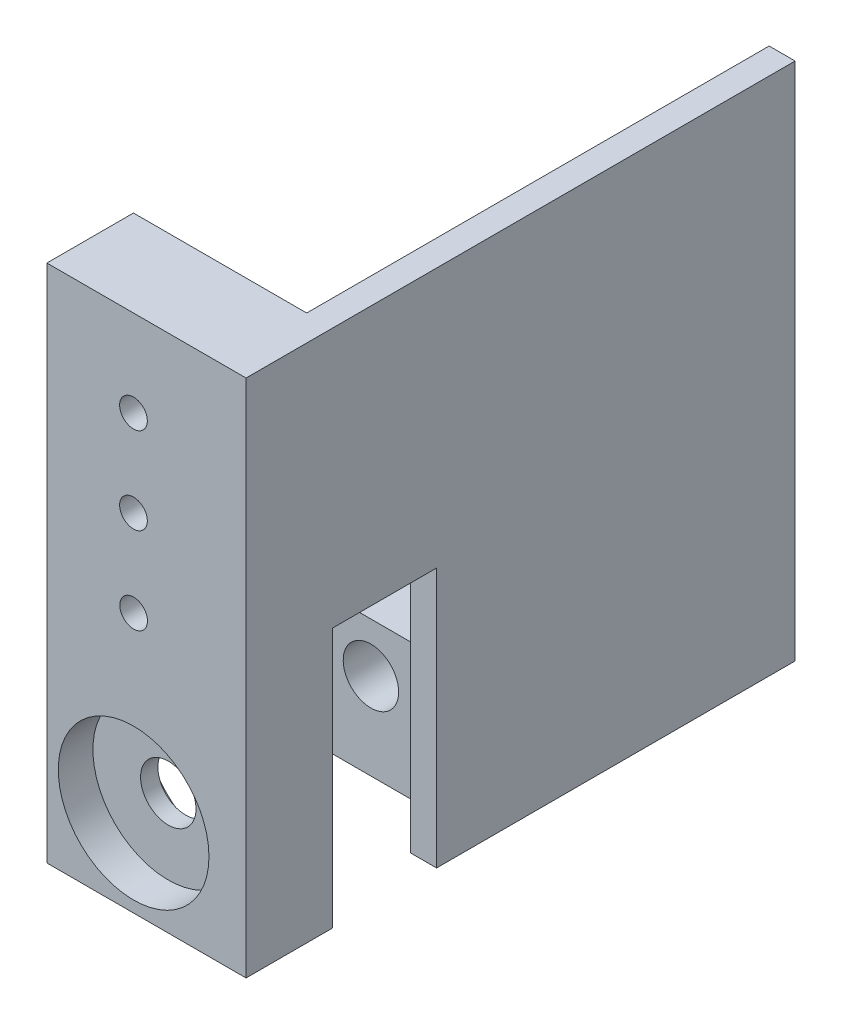
SolidWorks part; units mm, degrees
ref_plane "Front Plane" through (0, 0, 0) normal (0, 0, 1) x (1, 0, 0)
ref_plane "Top Plane" through (0, 0, 0) normal (0, 1, 0) x (1, 0, 0)
ref_plane "Right Plane" through (0, 0, 0) normal (1, 0, 0) x (0, 0, -1)
sketch "Sketch1" plane through (0, 0, 0) normal (0, 0, 1) x (1, 0, 0)
  line L1 (4.6927, -4.5791) -> (33.9027, -4.5791)
  line L2 (4.6927, -4.5791) -> (4.6927, -80.7791)
  line L3 (4.6927, -80.7791) -> (33.9027, -80.7791)
  line L4 (33.9027, -4.5791) -> (33.9027, -80.7791)
  dimension "D1" = 29.21
  dimension "D2" = 76.2
extrude "Boss-Extrude1" add sketch "Sketch1" along normal blind 12.7
sketch "Sketch3" plane through (0, 0, 12.7) normal (0, 0, 1) x (1, 0, 0)
  line L0 (33.9027, -80.7791) -> (33.9027, -4.5791) construction
  line L1 (33.9027, -4.5791) -> (4.6927, -4.5791) construction
  line L2 (17.3927, -4.5791) -> (17.3927, -80.7791) construction
  line L4 (4.6927, -80.7791) -> (33.9027, -80.7791) construction
  circle A0 centre (17.4135, -42.6791) radius 2.032
  circle A1 centre (17.3927, -29.9791) radius 2.032
  circle A2 centre (17.3927, -17.2791) radius 2.032
  dimension "D1" = 12.7
  dimension "D2" = 4.064
  dimension "D3" = 4.064
  dimension "D4" = 4.064
  dimension "D5" = 12.7
  dimension "D6" = 12.7
  dimension "D7" = 16.51
  dimension "D8" = 0
extrude "Cut-Extrude1" cut sketch "Sketch3" against normal blind 25.4
sketch "Sketch4" plane through (0, 0, 12.7) normal (0, 0, 1) x (1, 0, 0)
  circle A1 centre (17.4135, -68.0791) radius 4.064
  circle A3 centre (17.4135, -42.6791) radius 2.032 construction
  dimension "D1" = 25.4
  dimension "D2" = 8.128
sketch "Sketch17" plane through (0, 0, 0) normal (0, 0, -1) x (-1, 0, 0)
  line L0 (-4.6927, -80.7791) -> (-33.9027, -80.7791) construction
  line L1 (-33.9027, -4.5791) -> (-30.0927, -4.5791)
  line L2 (-33.9027, -4.5791) -> (-33.9027, -80.7791)
  line L3 (-33.9027, -80.7791) -> (-30.0927, -80.7791)
  line L4 (-30.0927, -4.5791) -> (-30.0927, -80.7791)
  dimension "D1" = 3.81
extrude "Boss-Extrude13" add sketch "Sketch17" along normal blind 67.818
sketch "Sketch18" plane through (30.0927, 0, 0) normal (-1, 0, 0) x (0, 0, 1)
  line L1 (-67.818, -80.7791) -> (-64.008, -80.7791)
  line L2 (-67.818, -80.7791) -> (-67.818, -60.4591)
  line L3 (-67.818, -60.4591) -> (-64.008, -60.4591)
  line L4 (-64.008, -80.7791) -> (-64.008, -60.4591)
  dimension "D1" = 20.32
  dimension "D2" = 3.81
extrude "Boss-Extrude14" add sketch "Sketch18" along normal blind 25.4
sketch "Sketch19" plane through (30.0927, 0, 0) normal (-1, 0, 0) x (0, 0, 1)
  line L0 (-64.008, -80.7791) -> (0, -80.7791) construction
  line L1 (-22.098, -80.7791) -> (-51.308, -80.7791)
  line L2 (-22.098, -80.7791) -> (-22.098, -60.8301)
  line L3 (-22.098, -60.8301) -> (-51.308, -60.8301)
  line L4 (-51.308, -80.7791) -> (-51.308, -60.8301)
  line L5 (-64.008, -80.7791) -> (-64.008, -60.4591) construction
  dimension "D1" = 12.7
  dimension "D2" = 29.21
extrude "Boss-Extrude15" add sketch "Sketch19" along normal blind 25.4
extrude "Cut-Extrude5" cut sketch "Sketch4" against normal through all contours A1
sketch "Sketch21" plane through (0, 0, 0) normal (0, 0, -1) x (-1, 0, 0)
  circle A0 centre (-17.4135, -68.0791) radius 11.049
  circle A1 centre (-17.4135, -68.0791) radius 4.064
  dimension "D1" = 22.098
  dimension "D2" = 8.128
extrude "Cut-Extrude6" cut sketch "Sketch21" against normal blind 5.08
sketch "Sketch22" plane through (0, 0, 12.7) normal (0, 0, 1) x (1, 0, 0)
  circle A0 centre (17.4135, -68.0791) radius 11.049
  circle A1 centre (17.4135, -68.0791) radius 4.064
  dimension "D1" = 22.098
  dimension "D2" = 8.128
extrude "Cut-Extrude7" cut sketch "Sketch22" against normal blind 5.08
sketch "Sketch23" plane through (30.0927, 0, 0) normal (-1, 0, 0) x (0, 0, 1)
  line L1 (0, -80.7791) -> (-15.24, -80.7791)
  line L2 (0, -80.7791) -> (0, -42.6791)
  line L3 (0, -42.6791) -> (-15.24, -42.6791)
  line L4 (-15.24, -80.7791) -> (-15.24, -42.6791)
  dimension "D1" = 38.1
  dimension "D2" = 15.24
extrude "Cut-Extrude8" cut sketch "Sketch23" against normal through all
sketch "Sketch24" plane through (0, -80.7791, 0) normal (0, -1, 0) x (1, 0, 0)
  line L1 (6.0824, -24.0843) -> (30.0949, -24.0843)
  line L2 (6.0824, -24.0843) -> (6.0824, -49.5327)
  line L3 (6.0824, -49.5327) -> (30.0949, -49.5327)
  line L4 (30.0949, -24.0843) -> (30.0949, -49.5327)
extrude "Cut-Extrude9" cut sketch "Sketch24" against normal blind 7.62
